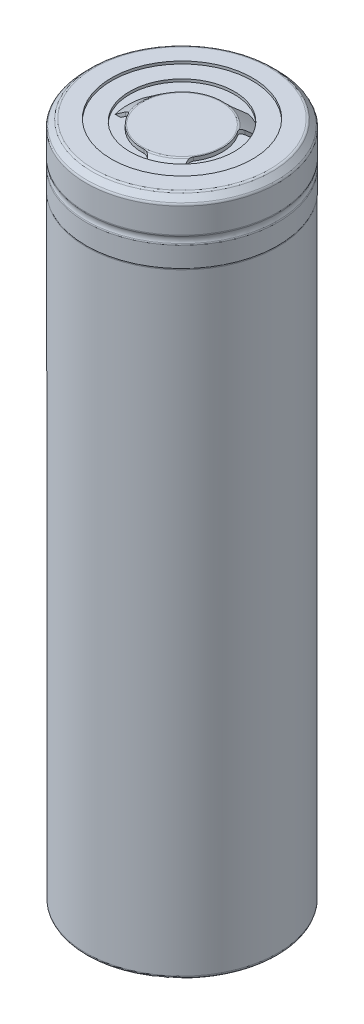
SolidWorks part; units mm, degrees
ref_plane "Ebene vorne" through (0, 0, 0) normal (0, 0, 1) x (1, 0, 0)
ref_plane "Ebene oben" through (0, 0, 0) normal (0, 1, 0) x (1, 0, 0)
ref_plane "Ebene rechts" through (0, 0, 0) normal (1, 0, 0) x (0, 0, -1)
sketch "Sketch1" plane through (0, 0, 0) normal (0, 0, 1) x (1, 0, 0)
  line L0 (0, 66.5966) -> (0, -169.2654) construction
  line L1 (0, -55) -> (0, 55) construction
  line L2 (0, 37.6239) -> (-3.7525, 37.6239)
  line L3 (-3.9289, 37.5666) -> (-5.2264, 36.6239)
  line L4 (-5.2264, 36.6239) -> (-8.54, 36.6239)
  line L5 (-8.54, 36.6239) -> (-8.54, 37.6239)
  line L6 (-8.54, 37.6239) -> (-5, 37.6239)
  line L7 (-5, 37.6239) -> (-5, 37.8739)
  line L8 (-5, 37.8739) -> (-6.75, 37.8739)
  line L9 (-6.75, 37.8739) -> (-6.75, 38.1239)
  line L10 (-6.75, 38.1239) -> (-8.54, 38.1239)
  line L11 (-8.54, 38.1239) -> (-9.19, 37.4739)
  line L12 (-9.19, 37.4739) -> (-9.19, 34.8739)
  line L13 (-9.19, 34.1739) -> (-9.19, 32.1739)
  line L14 (-9.19, 32.1739) -> (-9.16, 32.1739)
  line L15 (-9.16, 32.1739) -> (-9.16, -26.8261)
  line L16 (-9.16, -26.8261) -> (-6.75, -26.8261)
  line L17 (-6.75, -26.8261) -> (-6.75, -26.5761)
  line L18 (-6.75, -26.5761) -> (0, -26.5761)
  line L19 (0, -26.5761) -> (0, 37.6239)
  line L20 (-9.1, 35.1081) -> (-9.1, 20.1498) construction
  line L21 (-4.716, 36.6239) -> (-3.7525, 37.3239)
  line L22 (-3.7525, 37.3239) -> (-1.5, 37.3239)
  line L23 (-1.5, 37.3239) -> (-1.5, 36.6239)
  line L24 (-1.5, 36.6239) -> (-4.716, 36.6239)
  arc A0 (-9.19, 34.8739) -> (-9.19, 34.1739) centre (-9.8256, 34.5239) cw
  arc A1 (-3.9289, 37.5666) -> (-3.7525, 37.6239) centre (-3.7525, 37.3239) cw
  point P41 (-3.85, 37.6239)
  dimension "D1" = 18.38
  dimension "D5" = 9.1
  dimension "D19" = 0.3
  dimension "D2" = 0.25
  dimension "D3" = 13.5
  dimension "D4" = 18.32
  dimension "D6" = 0.7
  dimension "D7" = 45
  dimension "D8" = 0.65
  dimension "D9" = 13.5
  dimension "D10" = 0.25
  dimension "D11" = 10
  dimension "D12" = 0.25
  dimension "D13" = 1.5
  dimension "D14" = 7.7
  dimension "D15" = 36
  dimension "D16" = 59
  dimension "D17" = 61
  dimension "D18" = 64.95
  dimension "D20" = 3
revolve "Revolve1" add sketch "Sketch1" angle 360 about L0
sketch "Sketch3" plane through (0, 37.6239, 0) normal (0, 1, 0) x (1, 0, 0)
  line L0 (-9.8854, 0) -> (0, 0) construction
  line L1 (-55, 0) -> (55, 0) construction
  line L2 (-5.049, -1.35) -> (-3.6056, -1.35)
  line L3 (0, 0) -> (-5.5721, -9.6512) construction
  line L4 (1.3554, -5.0476) -> (0.6336, -3.7975)
  line L5 (1.3554, 5.0476) -> (0.6336, 3.7975)
  line L6 (-5.049, 1.35) -> (-3.6056, 1.35)
  line L7 (3.6936, 3.6976) -> (2.9719, 2.4475)
  line L8 (3.6936, -3.6976) -> (2.9719, -2.4475)
  circle A0 centre (0, 0) radius 5.2264 construction
  circle A1 centre (0, 0) radius 5.2264 construction
  circle A2 centre (0, 0) radius 3.85 construction
  arc A3 (-3.6056, -1.35) -> (0.6336, -3.7975) centre (0, 0) ccw
  arc A4 (-5.049, -1.35) -> (1.3554, -5.0476) centre (0, 0) ccw
  arc A5 (-5.049, 1.35) -> (1.3554, 5.0476) centre (0, 0) cw
  arc A6 (-3.6056, 1.35) -> (0.6336, 3.7975) centre (0, 0) cw
  arc A7 (2.9719, -2.4475) -> (2.9719, 2.4475) centre (0, 0) ccw
  arc A8 (3.6936, -3.6976) -> (3.6936, 3.6976) centre (0, 0) ccw
  dimension "D1" = 1.35
  dimension "D2" = 60
extrude "Cut-Extrude1" cut sketch "Sketch3" against normal up to surface (1 mm away) up to face at (0, 36.6239, 8.54)
fillet "Fillet1" radius 0.3 6 edges at (0, -26.8261, 9.16) (0, 38.1239, 8.54) (0, 37.4739, 9.19) (0, 32.1739, 9.16) (0, 34.1739, 9.19) (0, 34.8739, 9.19)
fillet "Fillet3" radius 0.7 6 edges at (-3.6056, 37.4304, -1.35) (0.6336, 37.4304, -3.7975) (2.9719, 37.4304, -2.4475) (2.9719, 37.4304, 2.4475) (0.6336, 37.4304, 3.7975) (-3.6056, 37.4304, 1.35)
sketch "Sketch4" plane through (0, 0, 0) normal (1, 0, 0) x (0, 0, -1)
  line L0 (0, 11.1239) -> (0, -16.9174) construction
  line L1 (0, 11.1239) -> (-13.393, 11.1239) construction
  line L2 (-14.1578, 38.1239) -> (3.0998, 38.1239) construction
  line L3 (6.75, 38.1239) -> (-6.75, 38.1239) construction
  text T0 "INR18650-29E\r\nSAMSUNG SDI\r\n6         2H75" font "Technic" height 3
  dimension "D1" = 27
wrap "Wrap1" sketch "Sketch4" wrap type scribe source sketch "Sketch4"
